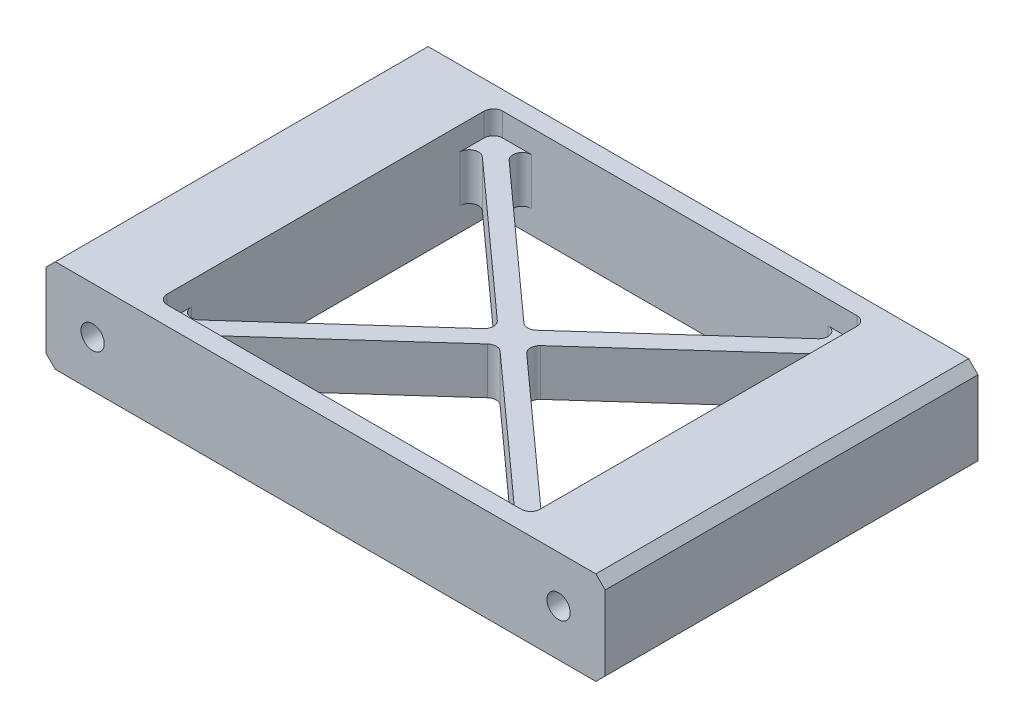
SolidWorks part; units mm, degrees
ref_plane "Спереди" through (0, 0, 0) normal (0, 0, 1) x (1, 0, 0)
ref_plane "Сверху" through (0, 0, 0) normal (0, 1, 0) x (1, 0, 0)
ref_plane "Справа" through (0, 0, 0) normal (1, 0, 0) x (0, 0, -1)
sketch "Эскиз1" plane through (0, 0, 0) normal (0, 1, 0) x (1, 0, 0)
  line L0 (0, 20) -> (0, -20) construction
  line L1 (-30, 20) -> (30, 20)
  line L2 (-30, 20) -> (-30, -20)
  line L3 (-30, -20) -> (30, -20)
  line L4 (30, 20) -> (30, -20)
  line L6 (-30, 0) -> (30, 0) construction
  point P8 (0, 0)
  dimension "D1" = 40
  dimension "D2" = 60
extrude "тело" add sketch "Эскиз1" along normal blind 5 and the other way blind 5
sketch "Эскиз5" plane through (0, 0, 20) normal (0, 0, 1) x (1, 0, 0)
  line L0 (-30, 0) -> (30, 0) construction
  line L1 (-30, -5) -> (-30, 5) construction
  line L2 (30, -5) -> (30, 5) construction
  line L4 (-30, 5) -> (30, 5) construction
  line L5 (0, 5) -> (0, -5) construction
  line L6 (-30, -5) -> (30, -5) construction
  circle A0 centre (-25, 0) radius 1.25
  circle A1 centre (25, 0) radius 1.25
  dimension "D1" = 2.5
  dimension "D2" = 5
  dimension "D3" = 50
extrude "отверстие под шурупы" cut sketch "Эскиз5" against normal through all
sketch "Эскиз6" plane through (0, 5, 0) normal (0, 1, 0) x (1, 0, 0)
  line L0 (-20, 18) -> (20, -18) construction
  line L1 (-20, 18) -> (20, 18) construction
  line L2 (-20, 18) -> (-20, -18) construction
  line L3 (-20, -18) -> (20, -18) construction
  line L4 (20, 18) -> (20, -18) construction
  line L5 (20, 18) -> (-20, -18) construction
  line L6 (-18.5052, 18) -> (18.5052, 18)
  line L7 (20, 16.6546) -> (20, -16.6546)
  line L8 (-18.5052, -18) -> (18.5052, -18)
  line L9 (-18.5052, 18) -> (0, 1.3454)
  line L11 (-20, 16.6546) -> (-20, -16.6546)
  line L12 (18.5052, 18) -> (0, 1.3454)
  line L13 (-20, 16.6546) -> (-1.4948, 0)
  line L14 (-18.5052, -18) -> (0, -1.3454)
  line L15 (-1.4948, 0) -> (-20, -16.6546)
  line L16 (1.4948, 0) -> (20, 16.6546)
  line L17 (1.4948, 0) -> (20, -16.6546)
  line L18 (0, -1.3454) -> (18.5052, -18)
  line L19 (0, 1.3454) -> (1.4948, 0) construction
  line L20 (-1.4948, 0) -> (0, 1.3454) construction
  line L21 (-1.4948, 0) -> (0, -1.3454) construction
  line L22 (1.4948, 0) -> (0, -1.3454) construction
  line L23 (30, 20) -> (-30, 20) construction
  line L24 (30, -20) -> (30, 20) construction
  point P4 (0, 0)
  point P13 (-20, 0)
  point P14 (-20, 0)
  point P16 (20, 0)
  point P18 (20, 0)
  point P19 (0, 18)
  point P20 (0, 18)
  point P21 (0, -18)
  point P22 (0, -18)
  point P23 (-0.7474, 0.6727)
  dimension "D1" = 2
  dimension "D2" = 2
  dimension "D3" = 10
extrude "ребра" cut sketch "Эскиз6" against normal through all
sketch "Эскиз7" plane through (0, 5, 0) normal (0, 1, 0) x (1, 0, 0)
  line L1 (-20, 18) -> (20, 18)
  line L2 (-20, 18) -> (-20, -18)
  line L3 (-20, -18) -> (20, -18)
  line L4 (20, 18) -> (20, -18)
extrude "углубления ребер" cut sketch "Эскиз7" against normal blind 2.5
mirror "Зеркальное отражение1" about plane through (0, 0, 0) normal (0, 1, 0) of "углубления ребер"
fillet "Скругление1" radius 1 16 edges at (-20, -3.75, -18) (-20, 3.75, -18) (-18.5052, 0, -18) (-20, 0, -16.6546) (20, -3.75, 18) (18.5052, 0, 18) (20, 0, 16.6546) (20, 3.75, 18) (-20, -3.75, 18) (-18.5052, 0, 18) (-20, 0, 16.6546) (-20, 3.75, 18) (20, -3.75, -18) (20, 0, -16.6546) (18.5052, 0, -18) (20, 3.75, -18)
fillet "Скругление2" radius 1 4 edges at (-1.4948, 0, 0) (0, 0, -1.3454) (1.4948, 0, 0) (0, 0, 1.3454)
chamfer "Фаска1" distance 1 angle 45 4 edges at (-30, 5, 0) (-30, -5, 0) (30, -5, 0) (30, 5, 0)
